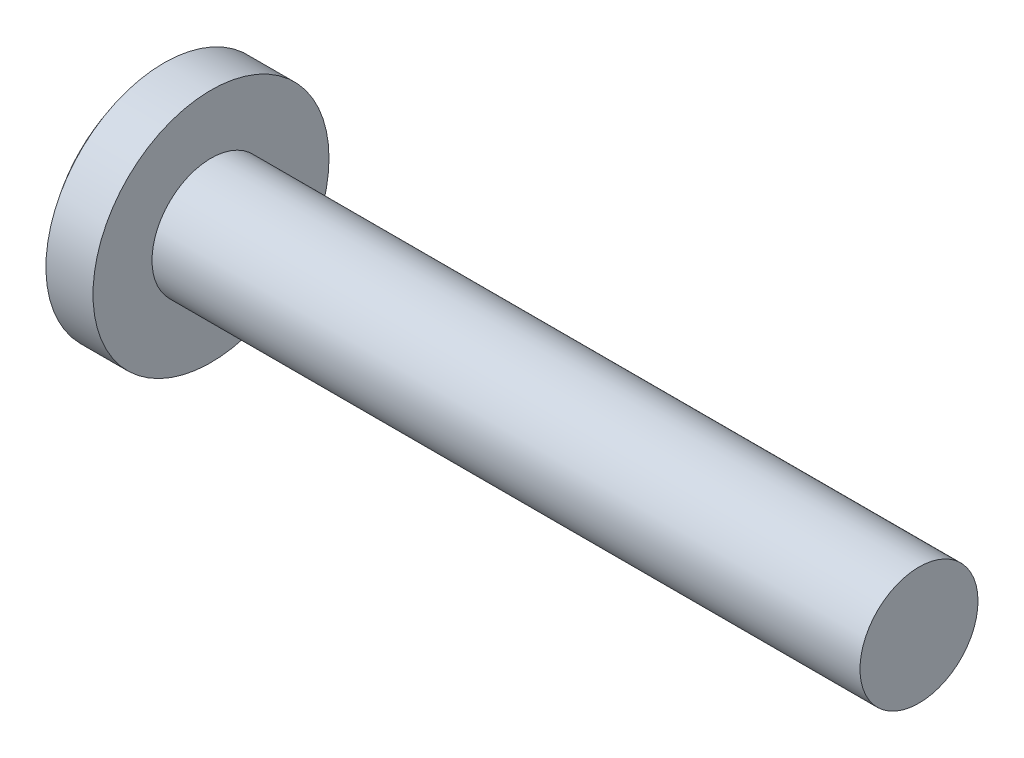
SolidWorks part; units mm, degrees
ref_plane "Front" through (0, 0, 0) normal (0, 0, 1) x (1, 0, 0)
ref_plane "Top" through (0, 0, 0) normal (0, 1, 0) x (1, 0, 0)
ref_plane "Right" through (0, 0, 0) normal (1, 0, 0) x (0, 0, -1)
sketch "Sketch1" plane through (0, 0, 0) normal (0, 0, 1) x (1, 0, 0)
  line L0 (67.5, 5) -> (10.5, 5)
  line L1 (7.5, 5.6) -> (7.5, 10)
  line L2 (7.5, 10) -> (3.51, 10)
  line L3 (10.5, 5) -> (7.7671, 5.3018) construction
  line L4 (67.5, 5) -> (67.5, 0)
  line L5 (4.5158, 0) -> (-13.5157, 0) construction
  line L6 (67.5, 0) -> (0, 0)
  line L7 (10.5, 5) -> (7.5, 5)
  line L8 (7.5, 5) -> (7.5, 5.6)
  arc A0 (3.51, 10) -> (0, 0) centre (16, 0) ccw
  arc A1 (7.5, 5.6) -> (7.7671, 5.3018) centre (7.8, 5.6) ccw construction
  dimension "D1" = 0.3
revolve "Base" add sketch "Sketch1" angle 360 about L5
cosmetic thread "ThreadCosmetic1" [suppressed] parameters "bb"=57, "THD_MINOR"=8.376
sketch "Sketch6" plane through (0, 0, 0) normal (1, 0, 0) x (0, 0, -1)
  line L0 (-1.9271, 0) -> (2.0512, 0) construction
  line L1 (0, 1.8651) -> (0, -2.0207) construction
  line L2 (1.01, 1.01) -> (1.01, 5.05)
  line L3 (1.01, 5.05) -> (-1.01, 5.05)
  line L4 (-1.01, 1.01) -> (-1.01, 5.05)
  line L5 (1.01, 1.01) -> (5.05, 1.01)
  line L6 (5.05, 1.01) -> (5.05, -1.01)
  line L7 (-5.05, 1.01) -> (-5.05, -1.01)
  line L8 (-1.01, 1.01) -> (-5.05, 1.01)
  line L9 (-1.01, -1.01) -> (-5.05, -1.01)
  line L10 (1.01, -1.01) -> (5.05, -1.01)
  line L11 (-1.01, -1.01) -> (-1.01, -5.05)
  line L12 (1.01, -5.05) -> (-1.01, -5.05)
  line L13 (1.01, -1.01) -> (1.01, -5.05)
  point P16 (-5.05, 0)
  point P17 (5.05, 0)
extrude "Cut-Extrude2" cut sketch "Sketch6" along normal blind 1.3
fillet "Fillet5" radius 0.3 4 edges at (0.6819, -1.01, 1.01) (0.6819, -1.01, -1.01) (0.6819, 1.01, 1.01) (0.6819, 1.01, -1.01)
draft "Draft2" type of draft neutral plane draft angle 30 neutral plane "Right" faces to draft 4 face at (1.0673, 0, 5.05) face at (1.0673, 5.05, 0) face at (1.0673, -5.05, 0) face at (1.0673, 0, -5.05) neutral plane through (0, 0, 0) neutral plane normal (1, 0, 0) reverse direction yes parameters "D1"=30
sketch "Sketch8" plane through (0, 0, 0) normal (0, 0, 1) x (1, 0, 0)
  line L0 (29.5, 5) -> (25.7, 4.188)
  line L1 (25.7, 4.188) -> (7.5, 4.188)
  line L2 (67.5, -5) -> (67.5, 5) construction
  line L3 (7.5, -10) -> (7.5, 10) construction
  line L6 (7.5, 4.188) -> (7.5, 10)
  line L7 (7.5, 10) -> (29.5, 10)
  line L8 (29.5, 10) -> (29.5, 5)
  line L9 (69.9753, 0) -> (60.4594, 0) construction
  dimension "x" = 3.8
sketch "Sketch10" plane through (0, 0, 0) normal (0, 0, 1) x (1, 0, 0)
  line L0 (67.5, 4.2968) -> (67.906, 5)
  line L1 (67.906, 5) -> (67.906, 5.812)
  line L2 (67.906, 5.812) -> (67.094, 5.812)
  line L3 (67.094, 5.812) -> (67.094, 5)
  line L4 (67.094, 5) -> (67.5, 4.2968)
  line L5 (0, 0) -> (78.5832, 0) construction
  line L6 (67.5, -5) -> (67.5, 5) construction
  dimension "D1" = 10
  dimension "D2" = 0.812
revolve "Cut-Revolve10" [suppressed] cut sketch "Sketch10" angle 360 about L5
pattern_linear "LPattern10" [suppressed] count 58 spacing 0.9744 along (-1, 0, 0) of bodies 105
equation "\"D1@Sketch6\" = \"m@Sketch6\" / 5"
equation "\"D1@Sketch10\" = \"d@Sketch1\""
equation "\"D2@Sketch10\" =  ( \"d@Sketch1\" - \"THD_MINOR@ThreadCosmetic1\" )  / 2"
equation "\"D3@LPattern10\" = \"D2@Sketch10\" * 1.2"
equation "\"D1@LPattern10\" = \"bb@ThreadCosmetic1\" / \"D3@LPattern10\" "
